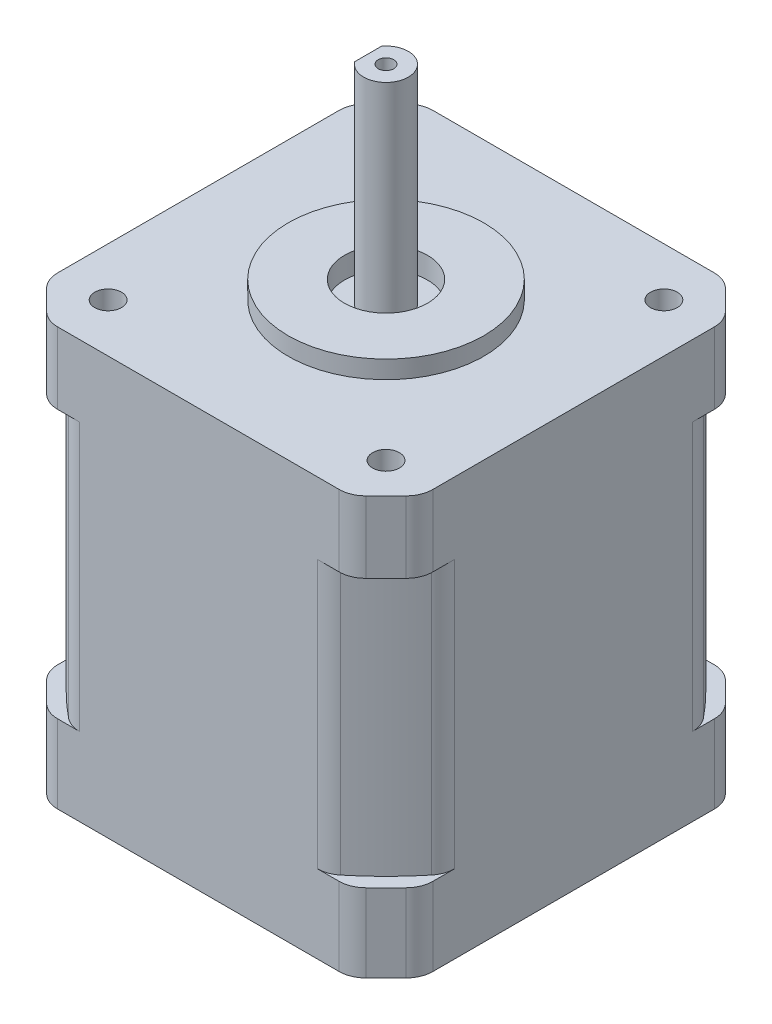
SolidWorks part; units mm, degrees
material "Chrome Stainless Steel"
ref_plane "Front Plane" through (0, 0, 0) normal (0, 0, 1) x (1, 0, 0)
ref_plane "Top Plane" through (0, 0, 0) normal (0, 1, 0) x (1, 0, 0)
ref_plane "Right Plane" through (0, 0, 0) normal (1, 0, 0) x (0, 0, -1)
sketch "Sketch1" plane through (0, 0, 0) normal (0, 1, 0) x (1, 0, 0)
  line L0 (21, 14.3553) -> (14.3553, 21) construction
  line L1 (-21, 21) -> (21, 21)
  line L2 (-21, 21) -> (-21, -21)
  line L3 (-21, -21) -> (21, -21)
  line L4 (21, 21) -> (21, -21)
  line L5 (-21, 21) -> (21, -21) construction
  line L6 (-21, -21) -> (21, 21) construction
  line L7 (-14.3553, -21) -> (-21, -14.3553) construction
  circle A0 centre (0, 0) radius 3.4079
  dimension "D1" = 42
  dimension "D2" = 42
  dimension "D3" = 50
  dimension "D4" = 45
extrude "Boss-Extrude1" add sketch "Sketch1" along normal blind 46.75 contours A0 | L4 L3 L2 L1
sketch "Sketch2" plane through (0, 46.75, 0) normal (0, 1, 0) x (1, 0, 0)
  circle A0 centre (0, 0) radius 10.95
  dimension "D1" = 21.9
extrude "Boss-Extrude2" add sketch "Sketch2" along normal blind 2
sketch "Sketch3" plane through (0, 46.75, 0) normal (0, 1, 0) x (1, 0, 0)
  line L0 (-14.3553, 21) -> (-21, 21)
  line L1 (-21, 21) -> (21, 21) construction
  line L2 (-21, 21) -> (-21, 14.3553)
  line L3 (-21, 21) -> (-21, -21) construction
  line L4 (-21, 14.3553) -> (-14.3553, 21) construction
  arc A0 (-21, 14.3553) -> (-14.3553, 21) centre (6.8471, -6.8471) cw
  dimension "D2" = 35
  dimension "D1" = 25
extrude "Cut-Extrude1" cut sketch "Sketch3" against normal blind 30 from offset 8 offset against normal yes
pattern_circular "CirPattern1" count 4 over 360 about axis through (0, 48.75, 0) along (0, -1, 0) of "Cut-Extrude1"
fillet "Fillet1" radius 3 8 edges at (21, 23.75, -14.3553) (21, 23.75, 14.3553) (14.3553, 23.75, 21) (-14.3553, 23.75, 21) (-21, 23.75, 14.3553) (14.3553, 23.75, -21) (-14.3553, 23.75, -21) (-21, 23.75, -14.3553)
chamfer "Chamfer1" distance 4 angle 45 8 edges at (-21, 42.75, 21) (-21, 4.375, 21) (-21, 4.375, -21) (-21, 42.75, -21) (21, 4.375, 21) (21, 42.75, 21) (21, 4.375, -21) (21, 42.75, -21)
fillet "Fillet2" radius 3 16 edges at (17, 4.375, -21) (21, 4.375, -17) (21, 42.75, -17) (17, 42.75, -21) (-17, 42.75, -21) (-17, 4.375, -21) (-21, 42.75, -17) (-21, 4.375, -17) (-17, 4.375, 21) (-21, 4.375, 17) (-21, 42.75, 17) (-17, 42.75, 21) (21, 42.75, 17) (21, 4.375, 17) (17, 4.375, 21) (17, 42.75, 21)
sketch "Sketch4" plane through (0, 48.75, 0) normal (0, 1, 0) x (1, 0, 0)
  circle A0 centre (0, 0) radius 4.65
  dimension "D1" = 9.3
extrude "Cut-Extrude2" cut sketch "Sketch4" against normal blind 2.4
other "DeleteFace1" face at (0, 0, 3.4079) and patch yes
sketch "Sketch5" plane through (0, 46.35, 0) normal (0, 1, 0) x (1, 0, 0)
  circle A0 centre (0, 0) radius 2.5
  dimension "D1" = 5
extrude "Boss-Extrude3" add sketch "Sketch5" along normal blind 23.25
sketch "Sketch6" plane through (0, 69.6, 0) normal (0, 1, 0) x (1, 0, 0)
  line L0 (-2, 1.5) -> (-2, -1.5)
  line L1 (-2, 0) -> (2.5, 0) construction
  circle A0 centre (0, 0) radius 2.5 construction
  circle A1 centre (0, 0) radius 2.5 construction
  arc A2 (-2, 1.5) -> (-2, -1.5) centre (-6.2467, 0) ccw
  dimension "D1" = 4.5
extrude "Cut-Extrude3" cut sketch "Sketch6" against normal blind 15.25
sketch "Sketch7" plane through (0, 69.6, 0) normal (0, 1, 0) x (1, 0, 0)
  circle A0 centre (0, 0) radius 0.875
  dimension "D1" = 1.75
extrude "Cut-Extrude4" cut sketch "Sketch7" against normal blind 2
sketch "Sketch8" plane through (0, 46.75, 0) normal (0, 1, 0) x (1, 0, 0)
  line L0 (0, 0) -> (-22, 0) construction
  line L1 (0, 0) -> (-15.5563, 15.5563) construction
  circle A0 centre (0, 0) radius 22 construction
  circle A1 centre (-15.5563, 15.5563) radius 1.5
  circle A2 centre (15.5563, 15.5563) radius 1.5
  circle A3 centre (15.5563, -15.5563) radius 1.5
  circle A4 centre (-15.5563, -15.5563) radius 1.5
  point P15 (0, 0)
  dimension "D1" = 44
  dimension "D3" = 3
  dimension "D2" = 45
  dimension "D4" = 4
extrude "Cut-Extrude5" cut sketch "Sketch8" against normal blind 5
